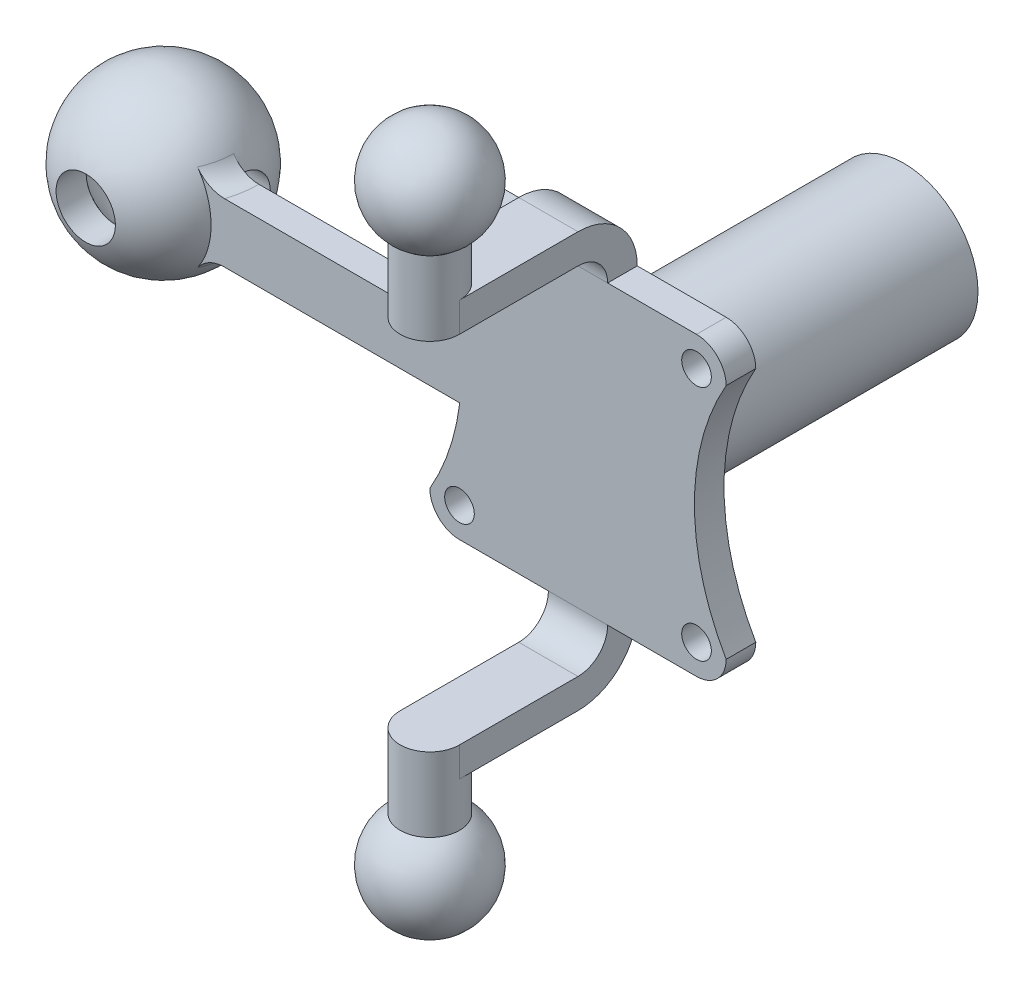
SolidWorks part; units mm, degrees
material "201 Annealed Stainless Steel (SS)"
ref_plane "Front Plane" through (0, 0, 0) normal (0, 0, 1) x (1, 0, 0)
ref_plane "Top Plane" through (0, 0, 0) normal (0, 1, 0) x (1, 0, 0)
ref_plane "Right Plane" through (0, 0, 0) normal (1, 0, 0) x (0, 0, -1)
sketch "Sketch2" plane through (0, 0, 0) normal (0, 0, 1) x (1, 0, 0)
  line L1 (-40, 50) -> (40, 50)
  line L2 (-50, 40) -> (-50, -40)
  line L3 (-40, -50) -> (40, -50)
  line L4 (50, 40) -> (50, -40)
  line L5 (-50, 50) -> (50, -50) construction
  line L6 (-50, -50) -> (50, 50) construction
  arc A0 (50, 40) -> (40, 50) centre (40, 40) ccw
  arc A1 (40, -50) -> (50, -40) centre (40, -40) ccw
  arc A2 (-50, 40) -> (-40, 50) centre (-40, 40) cw
  arc A3 (-50, -40) -> (-40, -50) centre (-40, -40) ccw
  point P0 (0, 0)
  dimension "D1" = 10
extrude "Boss-Extrude1" add sketch "Sketch2" along normal blind 10
sketch "Sketch3" plane through (0, 0, 10) normal (0, 0, 1) x (1, 0, 0)
  line L0 (-50, 40) -> (-50, -40) construction
  line L1 (-50, 40) -> (-50, -40)
  line L2 (50, 40) -> (50, -40)
  arc A0 (-50, 40) -> (-50, -40) centre (-119.282, 0) cw
  arc A1 (-50, -40) -> (-40, -50) centre (-40, -40) ccw construction
  arc A2 (50, 40) -> (50, -40) centre (119.282, 0) ccw
extrude "Cut-Extrude1" cut sketch "Sketch3" against normal blind 10
ref_plane "Plane1" through (-40, -50, 10) normal (1, 0, 0) x (0, 0, -1)
sketch "Sketch6" plane through (0, -50, 0) normal (0, -1, 0) x (1, 0, 0)
  line L1 (-40, 0) -> (40, 0) construction
  line L2 (-40, 10) -> (40, 10) construction
  line L3 (-10, 0) -> (10, 0)
  line L4 (-10, 0) -> (-10, 10)
  line L5 (-10, 10) -> (10, 10)
  line L6 (10, 0) -> (10, 10)
  point P0 (0, 0)
  point P1 (-10, 0)
extrude "Boss-Extrude5" add sketch "Sketch6" along normal blind 10
sketch "Sketch7" plane through (0, 0, 0) normal (0, 0, 1) x (1, 0, 0)
  line L1 (-10, -60) -> (10, -60)
  line L2 (-10, -60) -> (-10, -70)
  line L3 (-10, -70) -> (10, -70)
  line L4 (10, -60) -> (10, -70)
extrude "Boss-Extrude6" add sketch "Sketch7" along normal blind 60
fillet "Fillet7" radius 20 1 edges at (0, -70, 0)
fillet "Fillet8" radius 10 1 edges
sketch "Sketch8" plane through (0, -60, 0) normal (0, 1, 0) x (1, 0, 0)
  line L0 (10, -60) -> (-10, -60)
  arc A0 (-10, -60) -> (10, -60) centre (0, -60) ccw
extrude "Boss-Extrude7" add sketch "Sketch8" against normal blind 10
sketch "Sketch14" plane through (0, 0, 10) normal (0, 0, 1) x (1, 0, 0)
  line L0 (-39.282, 0) -> (39.282, 0)
  line L1 (-40, 50) -> (40, 50)
  arc A0 (-50, -40) -> (-50, 40) centre (-119.282, 0) ccw construction
  arc A1 (50, 40) -> (50, -40) centre (119.282, 0) ccw construction
  arc A2 (-40, 50) -> (-50, 40) centre (-40, 40) ccw construction
  arc A3 (50, 40) -> (40, 50) centre (40, 40) ccw construction
  spline S0 degree 2 poles (-39.282, 0) (-39.3595, 21.3507) (-50, 40) knots 0 0 0 1 1 1
  spline S1 degree 2 poles (-50, 40) (-49.1421, 49.1421) (-40, 50) knots 0 0 0 1 1 1
  spline S2 degree 2 poles (40, 50) (49.1421, 49.1421) (50, 40) knots 0 0 0 1 1 1
  spline S3 degree 2 poles (50, 40) (39.3595, 21.3507) (39.282, 0) knots 0 0 0 1 1 1
  point P8 (-41.5547, 18.9332)
  point P9 (-47.0711, 47.0711)
  point P16 (47.0711, 47.0711)
  point P26 (41.5547, 18.9332)
extrude "Cut-Extrude7" cut sketch "Sketch14" against normal blind 18
mirror "Mirror2" about plane through (-39.282, 0, -8) normal (0, -1, 0) of "Boss-Extrude7", "Boss-Extrude5", "Boss-Extrude6", "Fillet8", "Fillet7", "Cut-Extrude1", "Boss-Extrude1"
sketch "Sketch16" plane through (0, 0, 0) normal (0, 0, -1) x (-1, 0, 0)
  circle A0 centre (0, 0) radius 25
sketch "Sketch19" plane through (0, 0, 10) normal (0, 0, 1) x (1, 0, 0)
  circle A0 centre (-40, 40) radius 5
  circle A1 centre (40, 40) radius 5
  circle A2 centre (-40, -40) radius 5
  circle A3 centre (40, -40) radius 5
  point P0 (0, 0)
  point P1 (-40, 40)
  point P3 (-40, -40)
  point P5 (40, -40)
  point P7 (40, 40)
extrude "Cut-Extrude9" cut sketch "Sketch19" against normal blind 30
sketch "Sketch20" plane through (0, 0, 10) normal (0, 0, 1) x (1, 0, 0)
sketch "Sketch21" plane through (0, 0, 10) normal (0, 0, 1) x (1, 0, 0)
  line L0 (-133.2926, 10.9937) -> (0, 20)
  line L1 (-133.2926, -10.9937) -> (0, -20)
  arc A0 (0, -20) -> (0, 20) centre (0, 0) ccw
  circle A1 centre (-150, 0) radius 20
  point P7 (-150, 0)
sketch "Sketch29" plane through (0, 70, 0) normal (0, 1, 0) x (1, 0, 0)
  circle A0 centre (0, -60) radius 10
extrude "Boss-Extrude16" add sketch "Sketch29" along normal blind 15
sketch "Sketch30" plane through (0, 0, 0) normal (1, 0, 0) x (0, 0, -1)
  line L0 (-60, 85) -> (-60, 135) construction
  line L1 (-50, 85) -> (-70, 85) construction
  line L2 (-60, 118.0278) -> (-60, 85)
  line L3 (-60, 85) -> (-50, 85)
  arc A0 (-50, 85) -> (-60, 118.0278) centre (-60, 100) ccw
revolve "Revolve2" add sketch "Sketch30" angle 360 about L0
sketch "Sketch31" plane through (0, -70, 0) normal (0, -1, 0) x (1, 0, 0)
  circle A0 centre (0, 60) radius 10
extrude "Boss-Extrude17" add sketch "Sketch31" along normal blind 15
sketch "Sketch32" plane through (0, 0, 0) normal (1, 0, 0) x (0, 0, -1)
  line L0 (-60, -85) -> (-60, -135) construction
  line L1 (-70, -85) -> (-50, -85) construction
  line L2 (-60, -118.0278) -> (-60, -85)
  line L3 (-60, -85) -> (-70, -85)
  arc A0 (-70, -85) -> (-60, -118.0278) centre (-60, -100) ccw
  point P4 (-60, -100)
revolve "Revolve3" add sketch "Sketch32" angle 360 about L0
sketch "Sketch33" plane through (0, 0, 10) normal (0, 0, 1) x (1, 0, 0)
  line L0 (-134, 10) -> (-39.9095, 10)
  line L1 (-134, -10) -> (-39.9095, -10)
  line L5 (-134, -10) -> (-134, 10)
  arc A0 (-50, -40) -> (-50, 40) centre (-119.282, 0) ccw construction
  arc A1 (-39.9095, 10) -> (-39.9095, -10) centre (-119.282, 0) cw
  point P1 (0, 0)
extrude "Boss-Extrude21" add sketch "Sketch33" against normal blind 10
sketch "Sketch34" plane through (0, 0, 0) normal (0, 0, 1) x (1, 0, 0)
  line L0 (-134, 0) -> (-184, 0) construction
  line L1 (-134, 10) -> (-134, -10) construction
  line L2 (-178, 0) -> (-168.868, 0)
  line L3 (-134, 10) -> (-123.8466, 10)
  line L4 (-39.9095, 10) -> (-134, 10) construction
  arc A0 (-134, 10) -> (-168.868, 0) centre (-150, 0) ccw
  arc A1 (-123.8466, 10) -> (-178, 0) centre (-150, 0) ccw
  point P5 (-150, 0)
revolve "Revolve5" add sketch "Sketch34" angle 360 about L0
fillet "Fillet9" radius 10 1 edges at (-124.3482, 10, 5.0978)
fillet "Fillet10" radius 10 1 edges at (-124.3482, -10, 5.0978)
sketch "Sketch35" plane through (0, 0, 0) normal (0, 0, 1) x (1, 0, 0)
  circle A0 centre (-150, 0) radius 10
extrude "Cut-Extrude11" cut sketch "Sketch35" along normal blind 30
extrude "Boss-Extrude22" add sketch "Sketch16" along normal blind 100
